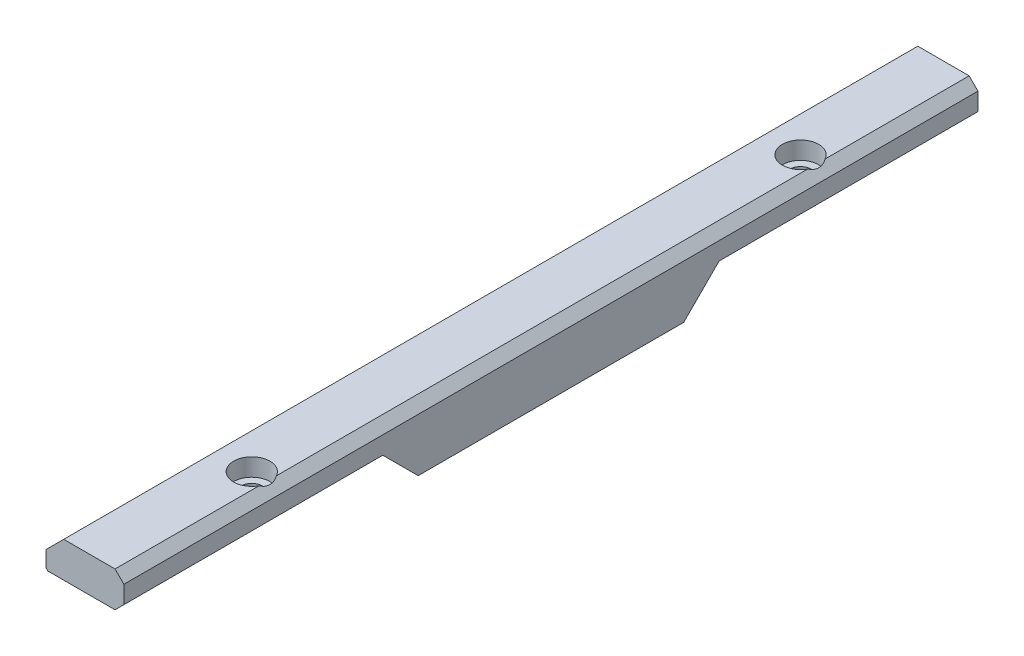
SolidWorks part; units mm, degrees
ref_plane "前视基准面" through (0, 0, 0) normal (0, 0, 1) x (1, 0, 0)
ref_plane "上视基准面" through (0, 0, 0) normal (0, 1, 0) x (1, 0, 0)
ref_plane "右视基准面" through (0, 0, 0) normal (1, 0, 0) x (0, 0, -1)
sketch "草图1" plane through (0, 0, 0) normal (0, 0, 1) x (1, 0, 0)
  line L1 (0, 0) -> (7, 0)
  line L3 (0, 4) -> (7, 4)
  line L4 (7, 0) -> (7, 4)
  line L5 (0, 4) -> (-1.8, 4)
  line L6 (0, 0) -> (0, -1.9)
  line L7 (0, -1.9) -> (-1.8, -1.9)
  line L8 (-1.8, 4) -> (-1.8, -1.9)
  dimension "D1" = 1.8
  dimension "D2" = 1.9
  dimension "D3" = 4
  dimension "D4" = 7
extrude "凸台-拉伸1" add sketch "草图1" against normal blind 96.5
sketch "草图2" plane through (0, 4, 0) normal (0, 1, 0) x (1, 0, 0)
  line L0 (4.2, 105.0677) -> (4.2, -16.3861) construction
  line L1 (-1.8, 96.5) -> (-1.8, 0) construction
  line L4 (-28.4042, 48.25) -> (44.7588, 48.25) construction
  line L7 (7, 0) -> (7, 96.5)
  line L8 (7, 0) -> (7, 96.5)
  line L9 (-1.8, 0) -> (7, 0)
  line L11 (7, 96.5) -> (-1.8, 96.5)
  line L12 (-1.8, 96.5) -> (-1.8, 0)
  line L13 (-1.8, 0) -> (7, 0) construction
  line L15 (7, 96.5) -> (-1.8, 96.5) construction
  circle A1 centre (4.2, 79.25) radius 2.05
  circle A3 centre (4.2, 17.25) radius 2.05
  circle A4 centre (4.2, 79.25) radius 1.2
  circle A7 centre (4.2, 17.25) radius 1.2
  dimension "D3" = 62
  dimension "D5" = 4.1
  dimension "D6" = 2.4
  dimension "D1" = 0
  dimension "D2" = 6
extrude "切除-拉伸1" cut sketch "草图2" against normal blind 10 and the other way through all contours A7 | A4
extrude "切除-拉伸2" cut sketch "草图2<3>" against normal blind 2 contours A1 | A3
sketch "草图2<3>" plane through (0, 4, 0) normal (0, 1, 0) x (1, 0, 0) same geometry as "草图2"
chamfer "倒角3" distance 2 angle 45 1 edges at (-1.8, 4, -48.25)
sketch "草图3" plane through (0, -1.9, 0) normal (0, -1, 0) x (1, 0, 0)
  line L0 (0, -96.5) -> (0, 0) construction
  line L1 (-1.8, -96.5) -> (0, -96.5)
  line L2 (-1.8, -96.5) -> (-1.8, -89.1)
  line L3 (-1.8, -89.1) -> (0, -89.1)
  line L4 (0, -96.5) -> (0, -89.1)
  line L5 (-1.8, 0) -> (0, 0)
  line L6 (-1.8, 0) -> (-1.8, -7.4)
  line L7 (-1.8, -7.4) -> (0, -7.4)
  line L8 (0, 0) -> (0, -7.4)
  dimension "D1" = 7.4
extrude "切除-拉伸3" cut sketch "草图3" against normal up to surface (1.9 mm away) up to face at (4.2, 0, -18.45)
chamfer "倒角4" distance 0.2 angle 45 8 edges at (0, -0.95, -89.1) (0, -0.95, -7.4) (0, -1.9, -48.25) (-1.8, 0, -92.8) (-1.8, -0.95, -89.1) (-1.8, 0, -3.7) (-1.8, -0.95, -7.4) (-1.8, -1.9, -48.25)
chamfer "倒角5" distance 0.6 angle 45 2 edges at (-0.9, -1.9, -89.1) (-0.9, -1.9, -7.4)
chamfer "倒角2" distance 1 angle 45 1 edges at (7, 4, -48.25)
sketch "草图4" plane through (0, 0, 0) normal (0, 1, 0) x (1, 0, 0)
  line L0 (7, 96.5) -> (7, 0) construction
  line L1 (7, 63.25) -> (5.7, 63.25)
  line L2 (7, 63.25) -> (7, 33.25)
  line L3 (7, 33.25) -> (5.7, 33.25)
  line L4 (5.7, 63.25) -> (5.7, 33.25)
  line L7 (-26.4563, 48.25) -> (40.4498, 48.25) construction
  line L8 (6, 96.5) -> (0.2, 96.5) construction
  line L9 (6, 0) -> (0.2, 0) construction
  dimension "D1" = 1.3
  dimension "D2" = 30
extrude "凸台-拉伸2" add sketch "草图4" against normal blind 3
chamfer "倒角6" distance 3 angle 45 2 edges at (6.35, 0, -33.25) (6.35, 0, -63.25)
chamfer "倒角1" distance 1 angle 45 2 edges at (7, 0, -15.125) (7, 0, -81.375)
chamfer "倒角7" distance 0.4 angle 45 1 edges at (5.7, -3, -48.25)
